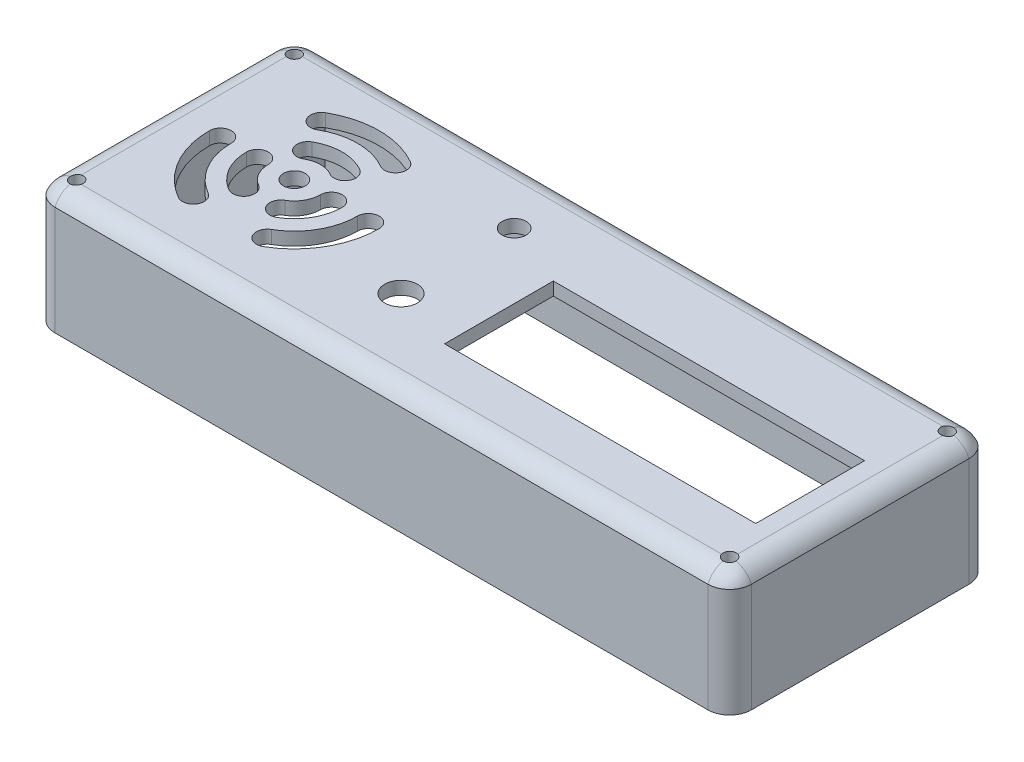
SolidWorks part; units mm, degrees
ref_plane "Front Plane" through (0, 0, 0) normal (0, 0, 1) x (1, 0, 0)
ref_plane "Top Plane" through (0, 0, 0) normal (0, 1, 0) x (1, 0, 0)
ref_plane "Right Plane" through (0, 0, 0) normal (1, 0, 0) x (0, 0, -1)
sketch "Sketch1" plane through (0, 0, 0) normal (0, 1, 0) x (1, 0, 0)
  line L1 (0, 5) -> (150, 5)
  line L2 (-5, 0) -> (-5, -50)
  line L3 (0, -55) -> (150, -55)
  line L4 (155, 0) -> (155, -50)
  arc A0 (150, 5) -> (155, 0) centre (150, 0) cw
  arc A1 (150, -55) -> (155, -50) centre (150, -50) ccw
  arc A2 (-5, -50) -> (0, -55) centre (0, -50) ccw
  arc A3 (0, 5) -> (-5, 0) centre (0, 0) ccw
  point P6 (155, 5)
  point P11 (-5, -55)
  point P14 (-5, 5)
  dimension "D3" = 5
  dimension "D1" = 60
  dimension "D2" = 160
extrude "Boss-Extrude1" add sketch "Sketch1" along normal blind 3
fillet "Fillet1" radius 5 8 edges at (-3.5355, 3, 53.5355) (-5, 3, 25) (-3.5355, 3, -3.5355) (75, 3, -5) (153.5355, 3, -3.5355) (155, 3, 25) (153.5355, 3, 53.5355) (75, 3, 55)
sketch "Sketch2" plane through (0, 3, 0) normal (0, 1, 0) x (1, 0, 0)
  circle A0 centre (0, -50) radius 1.5 construction
  circle A1 centre (0, -50) radius 1.5
  circle A2 centre (0, 0) radius 1.5 construction
  circle A3 centre (0, 0) radius 1.5
  circle A4 centre (150, -50) radius 1.5 construction
  circle A5 centre (150, -50) radius 1.5
  circle A6 centre (150, 0) radius 1.5 construction
  circle A7 centre (150, 0) radius 1.5
extrude "Cut-Extrude1" cut sketch "Sketch2" against normal through all both and the other way through all
sketch "Sketch3" plane through (0, 3, 0) normal (0, 1, 0) x (1, 0, 0)
  line L0 (4, -4) -> (46, -46) construction
  line L1 (4, -4) -> (46, -4) construction
  line L2 (4, -4) -> (4, -46) construction
  line L3 (4, -46) -> (46, -46) construction
  line L4 (46, -4) -> (46, -46) construction
  line L5 (25, -25) -> (25, -16.5) construction
  line L6 (25, -25) -> (32.3612, -29.25) construction
  line L7 (25, -25) -> (17.6388, -29.25) construction
  line L8 (25, -16.5) -> (25, -8) construction
  line L9 (17.6388, -29.25) -> (10.2776, -33.5) construction
  line L10 (32.3612, -29.25) -> (39.7224, -33.5) construction
  line L11 (25, -25) -> (32.3612, -20.75) construction
  line L12 (32.3612, -20.75) -> (39.7224, -16.5) construction
  line L13 (25, -25) -> (25, -33.5) construction
  line L14 (25, -33.5) -> (25, -42) construction
  line L15 (25, -25) -> (17.6388, -20.75) construction
  line L16 (17.6388, -20.75) -> (10.2776, -16.5) construction
  line L17 (25, -25) -> (20.75, -17.6388) construction
  line L18 (20.75, -17.6388) -> (16.5, -10.2776) construction
  line L19 (25, -25) -> (29.25, -17.6388) construction
  line L20 (29.25, -17.6388) -> (33.5, -10.2776) construction
  line L21 (25, -25) -> (33.5, -25) construction
  line L22 (33.5, -25) -> (42, -25) construction
  line L23 (25, -25) -> (29.25, -32.3612) construction
  line L24 (29.25, -32.3612) -> (33.5, -39.7224) construction
  line L25 (25, -25) -> (20.75, -32.3612) construction
  line L26 (20.75, -32.3612) -> (16.5, -39.7224) construction
  line L27 (25, -25) -> (16.5, -25) construction
  line L28 (16.5, -25) -> (8, -25) construction
  circle A0 centre (46, -46) radius 1 construction
  circle A1 centre (46, -4) radius 1 construction
  circle A2 centre (4, -4) radius 1 construction
  circle A3 centre (4, -46) radius 1 construction
  circle A4 centre (46, -46) radius 1 construction
  circle A5 centre (46, -4) radius 1 construction
  circle A6 centre (4, -4) radius 1 construction
  circle A7 centre (4, -46) radius 1 construction
  circle A8 centre (25, -25) radius 19.5 construction
  circle A9 centre (25, -25) radius 2.5
  arc A10 (25, -16.5) -> (17.6388, -29.25) centre (25, -25) ccw construction
  arc A11 (17.6388, -29.25) -> (32.3612, -29.25) centre (25, -25) ccw construction
  arc A12 (32.3612, -29.25) -> (25, -16.5) centre (25, -25) ccw construction
  arc A13 (25, -8) -> (10.2776, -33.5) centre (25, -25) ccw construction
  arc A14 (10.2776, -33.5) -> (39.7224, -33.5) centre (25, -25) ccw construction
  arc A15 (39.7224, -33.5) -> (25, -8) centre (25, -25) ccw construction
  arc A16 (20.75, -17.6388) -> (29.25, -17.6388) centre (25, -25) cw construction
  arc A17 (30.5, -15.4737) -> (19.5, -15.4737) centre (25, -25) ccw
  arc A18 (28, -19.8038) -> (22, -19.8038) centre (25, -25) ccw
  arc A19 (28, -19.8038) -> (30.5, -15.4737) centre (29.25, -17.6388) ccw
  arc A20 (19.5, -15.4737) -> (22, -19.8038) centre (20.75, -17.6388) ccw
  arc A21 (33.5, -25) -> (29.25, -32.3612) centre (25, -25) cw construction
  arc A26 (30.5, -34.5263) -> (36, -25) centre (25, -25) ccw
  arc A27 (28, -30.1962) -> (31, -25) centre (25, -25) ccw
  arc A28 (28, -30.1962) -> (30.5, -34.5263) centre (29.25, -32.3612) ccw
  arc A29 (36, -25) -> (31, -25) centre (33.5, -25) ccw
  arc A30 (16.5, -25) -> (20.75, -32.3612) centre (25, -25) ccw construction
  arc A31 (14, -25) -> (19.5, -34.5263) centre (25, -25) ccw
  arc A32 (19, -25) -> (22, -30.1962) centre (25, -25) ccw
  arc A33 (19, -25) -> (14, -25) centre (16.5, -25) ccw
  arc A34 (19.5, -34.5263) -> (22, -30.1962) centre (20.75, -32.3612) ccw
  arc A35 (16.5, -10.2776) -> (33.5, -10.2776) centre (25, -25) cw construction
  arc A36 (34.75, -8.1125) -> (15.25, -8.1125) centre (25, -25) ccw
  arc A37 (32.25, -12.4426) -> (17.75, -12.4426) centre (25, -25) ccw
  arc A38 (32.25, -12.4426) -> (34.75, -8.1125) centre (33.5, -10.2776) ccw
  arc A39 (15.25, -8.1125) -> (17.75, -12.4426) centre (16.5, -10.2776) ccw
  arc A40 (42, -25) -> (33.5, -39.7224) centre (25, -25) cw construction
  arc A41 (34.75, -41.8875) -> (44.5, -25) centre (25, -25) ccw
  arc A42 (32.25, -37.5574) -> (39.5, -25) centre (25, -25) ccw
  arc A43 (32.25, -37.5574) -> (34.75, -41.8875) centre (33.5, -39.7224) ccw
  arc A44 (44.5, -25) -> (39.5, -25) centre (42, -25) ccw
  arc A45 (8, -25) -> (16.5, -39.7224) centre (25, -25) ccw construction
  arc A46 (5.5, -25) -> (15.25, -41.8875) centre (25, -25) ccw
  arc A47 (10.5, -25) -> (17.75, -37.5574) centre (25, -25) ccw
  arc A48 (10.5, -25) -> (5.5, -25) centre (8, -25) ccw
  arc A49 (15.25, -41.8875) -> (17.75, -37.5574) centre (16.5, -39.7224) ccw
  point P32 (25, -16.5)
  point P51 (32.3612, -29.25)
  point P58 (17.6388, -29.25)
  point P64 (25, -8)
  point P70 (39.7224, -33.5)
  point P76 (10.2776, -33.5)
  dimension "D1" = 39
  dimension "D2" = 5
  dimension "D4" = 2.5
  dimension "D3" = 8.5
extrude "Cut-Extrude2" cut sketch "Sketch3" against normal through all both and the other way through all
sketch "Sketch4" plane through (0, 3, 0) normal (0, 1, 0) x (1, 0, 0)
  line L0 (150.4174, -48.5593) -> (150.4174, -1.4407) construction
  line L1 (74.9174, -15.4174) -> (146.4174, -15.4174)
  line L2 (74.9174, -15.4174) -> (74.9174, -40.4174)
  line L3 (74.9174, -40.4174) -> (146.4174, -40.4174)
  line L4 (146.4174, -15.4174) -> (146.4174, -40.4174)
  line L5 (1.4407, -50.4174) -> (148.5593, -50.4174) construction
  circle A0 centre (59.9174, -35.4174) radius 3.75
  circle A1 centre (59.9174, -35.4174) radius 9.5 construction
  circle A2 centre (59.9174, -9.4174) radius 2.75
  dimension "D5" = 7.5
  dimension "D6" = 19
  dimension "D7" = 5.5
  dimension "D1" = 25
  dimension "D2" = 71.5
  dimension "D3" = 4
  dimension "D4" = 10
  dimension "D8" = 15
  dimension "D9" = 26
  dimension "D10" = 15
extrude "Cut-Extrude3" cut sketch "Sketch4" against normal through all both and the other way through all
sketch "Sketch5" plane through (0, 0, 0) normal (0, -1, 0) x (1, 0, 0)
  line L0 (4, 53) -> (146, 53)
  line L1 (153, 46) -> (153, 4)
  line L2 (146, -3) -> (4, -3)
  line L3 (-3, 4) -> (-3, 46)
  line L4 (155, 0) -> (155, 50)
  line L5 (150, 55) -> (0, 55)
  line L6 (-5, 50) -> (-5, 0)
  line L7 (0, -5) -> (150, -5)
  line L8 (155, 0) -> (155, 50)
  line L9 (150, 55) -> (0, 55)
  line L10 (-5, 50) -> (-5, 0)
  line L11 (0, -5) -> (150, -5)
  circle A0 centre (0, 50) radius 1.5 construction
  circle A1 centre (0, 50) radius 1.5
  circle A2 centre (0, 0) radius 1.5 construction
  circle A3 centre (0, 0) radius 1.5
  circle A4 centre (150, 0) radius 1.5 construction
  circle A5 centre (150, 0) radius 1.5
  circle A6 centre (150, 50) radius 1.5 construction
  circle A7 centre (150, 50) radius 1.5
  circle A8 centre (0, 50) radius 5 construction
  circle A9 centre (0, 0) radius 5 construction
  circle A10 centre (150, 0) radius 5 construction
  circle A11 centre (150, 50) radius 5 construction
  arc A12 (150, -5) -> (155, 0) centre (150, 0) ccw
  arc A13 (155, 50) -> (150, 55) centre (150, 50) ccw
  arc A14 (0, 55) -> (-5, 50) centre (0, 50) ccw
  arc A15 (-5, 0) -> (0, -5) centre (0, 0) ccw
  arc A16 (150, -5) -> (155, 0) centre (150, 0) ccw
  arc A17 (155, 50) -> (150, 55) centre (150, 50) ccw
  arc A18 (0, 55) -> (-5, 50) centre (0, 50) ccw
  arc A19 (-5, 0) -> (0, -5) centre (0, 0) ccw
  arc A20 (-3, 46) -> (4, 53) centre (0, 50) ccw
  arc A21 (146, 53) -> (153, 46) centre (150, 50) ccw
  arc A22 (153, 4) -> (146, -3) centre (150, 0) ccw
  arc A23 (4, -3) -> (-3, 4) centre (0, 0) ccw
  dimension "D1" = 0
extrude "Boss-Extrude2" add sketch "Sketch5" along normal blind 25
